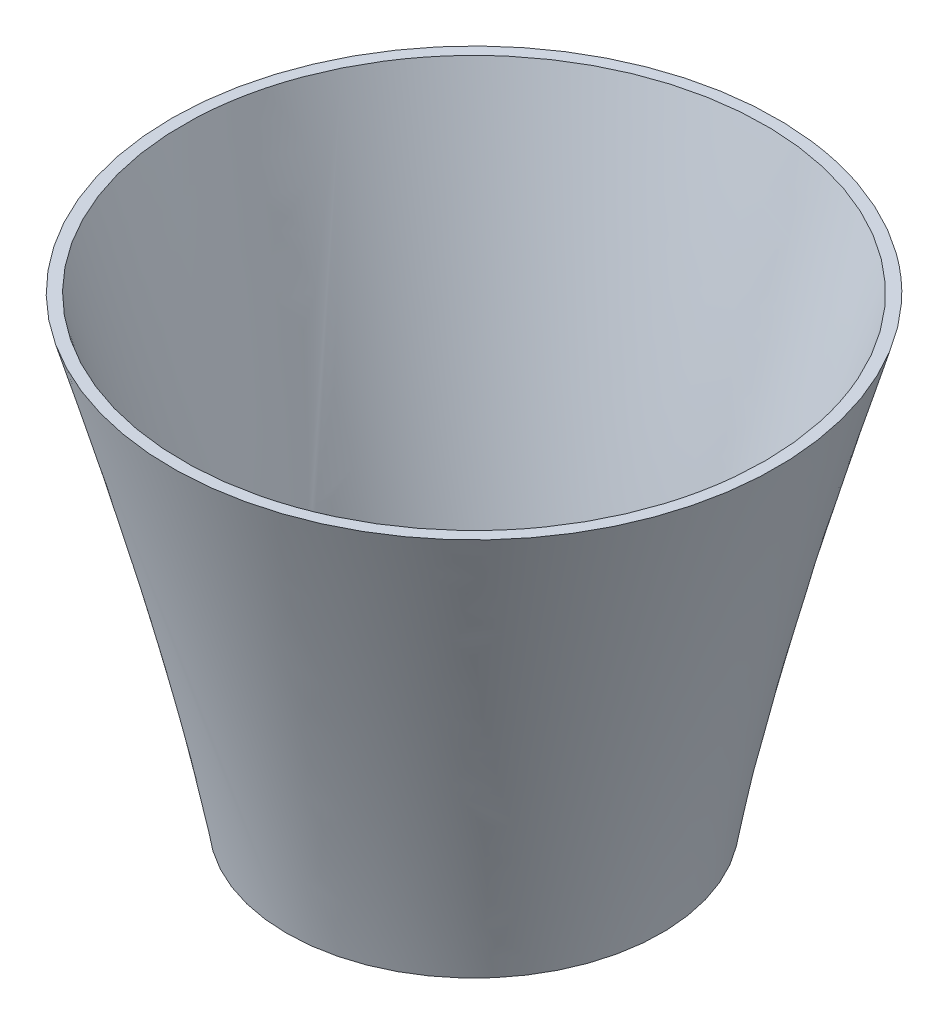
SolidWorks part; units mm, degrees
ref_plane "Ön Düzlem" through (0, 0, 0) normal (0, 0, 1) x (1, 0, 0)
ref_plane "Üst Düzlem" through (0, 0, 0) normal (0, 1, 0) x (1, 0, 0)
ref_plane "Sağ Düzlem" through (0, 0, 0) normal (1, 0, 0) x (0, 0, -1)
sketch "Çizim1" plane through (0, 0, 0) normal (0, 1, 0) x (1, 0, 0)
  circle A1 centre (0, 0) radius 32.5
  dimension "D1" = 65
ref_plane "Düzlem4" through (0, 80, 0) normal (0, 1, 0) x (1, 0, 0)
sketch "Çizim2" plane through (0, 80, 0) normal (0, 1, 0) x (1, 0, 0)
  circle A0 centre (0, 0) radius 52.5
  dimension "D1" = 105
loft "Loft1" add profiles "Çizim1", "Çizim2" connector at (0, 0, 32.5) connector at (-24.0693, 80, 46.6574)
sketch "Çizim3" plane through (0, 0, 0) normal (0, 1, 0) x (1, 0, 0)
  circle A0 centre (0, 0) radius 30.5
  dimension "D1" = 61
sketch "Çizim4" plane through (0, 80, 0) normal (0, 1, 0) x (1, 0, 0)
  circle A0 centre (0, 0) radius 50.5
  dimension "D1" = 101
loft "Kes-Loft1" cut profiles "Çizim4", "Çizim3" connector at (-45.2804, 80, -22.3593) connector at (-30.4996, 0, 0.1533)
